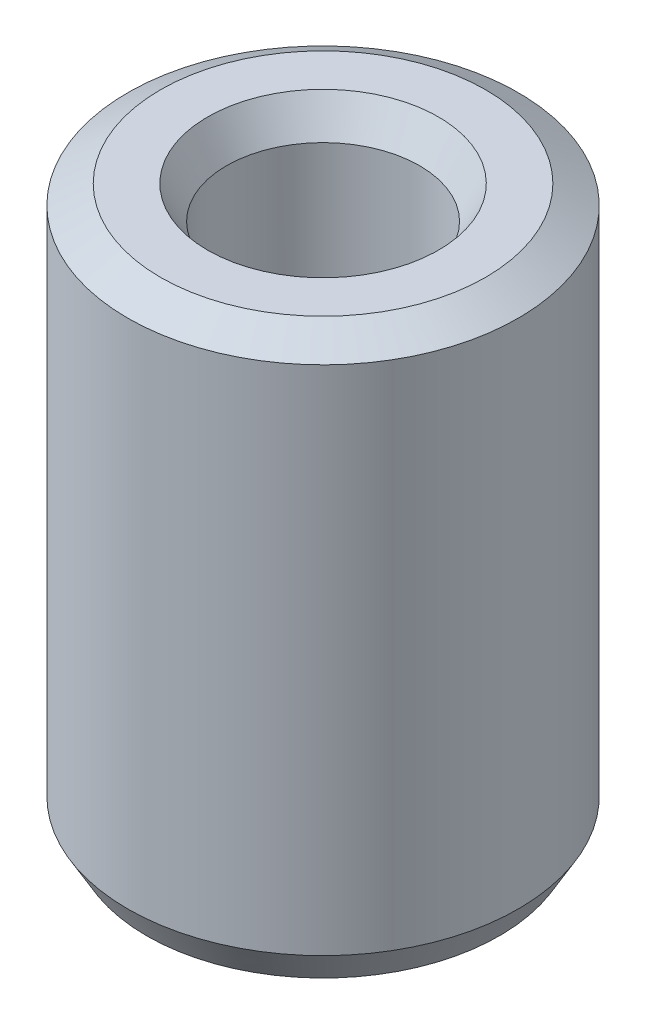
SolidWorks part; units mm, degrees
ref_plane "Front Plane" through (0, 0, 0) normal (0, 0, 1) x (1, 0, 0)
ref_plane "Top Plane" through (0, 0, 0) normal (0, 1, 0) x (1, 0, 0)
ref_plane "Right Plane" through (0, 0, 0) normal (1, 0, 0) x (0, 0, -1)
sketch "Sketch1" plane through (0, 0, 0) normal (0, 1, 0) x (1, 0, 0)
  circle A0 centre (0, 0) radius 15
  dimension "SLEEVE_OD" = 30
extrude "Boss-Extrude1" add sketch "Sketch1" along normal blind 43.2676
sketch "Sketch2" plane through (0, 0, 0) normal (0, 1, 0) x (1, 0, 0)
  circle A0 centre (0, 0) radius 7.4136
  dimension "BORE_D" = 14.8272
extrude "Cut-Extrude1" cut sketch "Sketch2" along normal through all
chamfer "Chamfer1" distance 1.4534 angle 60 4 edges at (0, 43.2676, 7.4136) (0, 0, 7.4136) (0, 0, 15) (0, 43.2676, 15) first distance on face at (0, 43.2676, 7.4136) first distance on face at (0, 0, 7.4136) first distance on face at (0, 43.2676, 15)
